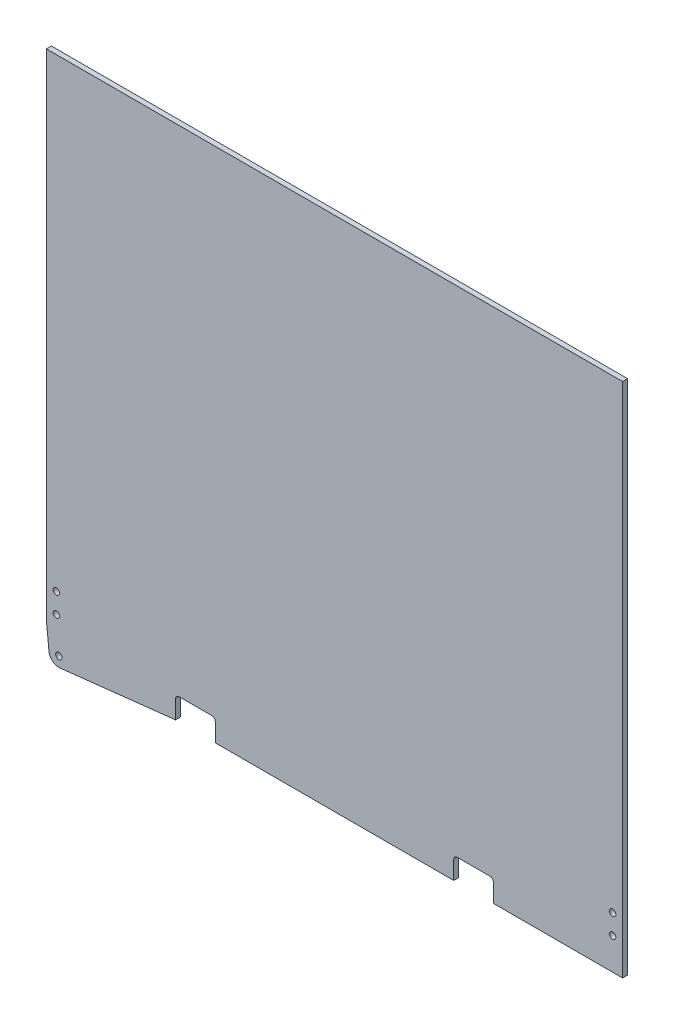
SolidWorks part; units mm, degrees
ref_plane "Front Plane" through (0, 0, 0) normal (0, 0, 1) x (1, 0, 0)
ref_plane "Top Plane" through (0, 0, 0) normal (0, 1, 0) x (1, 0, 0)
ref_plane "Right Plane" through (0, 0, 0) normal (1, 0, 0) x (0, 0, -1)
sketch "Sketch1" plane through (0, 0, 0) normal (0, 0, 1) x (1, 0, 0)
  line L0 (82.55, -20.32) -> (82.55, -6.35)
  line L2 (0, 0) -> (0, 309.88)
  line L3 (0, 309.88) -> (368.3, 309.88)
  line L4 (368.3, -20.32) -> (368.3, 309.88)
  line L5 (82.55, -6.35) -> (107.95, -6.35)
  line L6 (107.95, -6.35) -> (107.95, -20.32)
  line L7 (107.95, -20.32) -> (260.35, -20.32)
  line L8 (260.35, -20.32) -> (260.35, -6.35)
  line L9 (260.35, -6.35) -> (285.75, -6.35)
  line L10 (285.75, -6.35) -> (285.75, -20.32)
  line L11 (285.75, -20.32) -> (368.3, -20.32)
  line L12 (361.95, 12.7) -> (368.3, 12.7) construction
  line L13 (0, 0) -> (6.35, 0) construction
  line L14 (0.0315, -6.9818) -> (1.619, -22.8568)
  line L15 (8.6391, -28.5361) -> (82.55, -20.32)
  line L16 (0, 0) -> (0, -6.35)
  circle A0 centre (6.35, 0) radius 2.032
  circle A1 centre (6.35, 12.7) radius 2.032
  circle A2 centre (361.95, 0) radius 2.032
  circle A3 centre (361.95, 12.7) radius 2.032
  arc A5 (1.619, -22.8568) -> (8.6391, -28.5361) centre (7.9375, -22.225) ccw
  circle A6 centre (7.9375, -22.225) radius 2.032
  arc A7 (0, -6.35) -> (0.0315, -6.9818) centre (6.35, -6.35) ccw
  point P30 (0.2276, -4.0786)
  dimension "D6" = 4.064
  dimension "D10" = 6.35
  dimension "D11" = 4.064
  dimension "D2" = 330.2
  dimension "D3" = 13.97
  dimension "D4" = 25.4
  dimension "D5" = 152.4
  dimension "D7" = 12.7
  dimension "D8" = 6.35
  dimension "D9" = 20.32
  dimension "D12" = 22.225
  dimension "D13" = 1.5875
  dimension "D14" = 82.55
  dimension "D15" = 368.3
  dimension "D16" = 6.35
extrude "Boss-Extrude1" add sketch "Sketch1" along normal blind 3.175
fillet "Fillet1" radius 2.286 4 edges at (285.75, -6.35, 1.5875) (107.95, -6.35, 1.5875) (260.35, -6.35, 1.5875) (82.55, -6.35, 1.5875)
